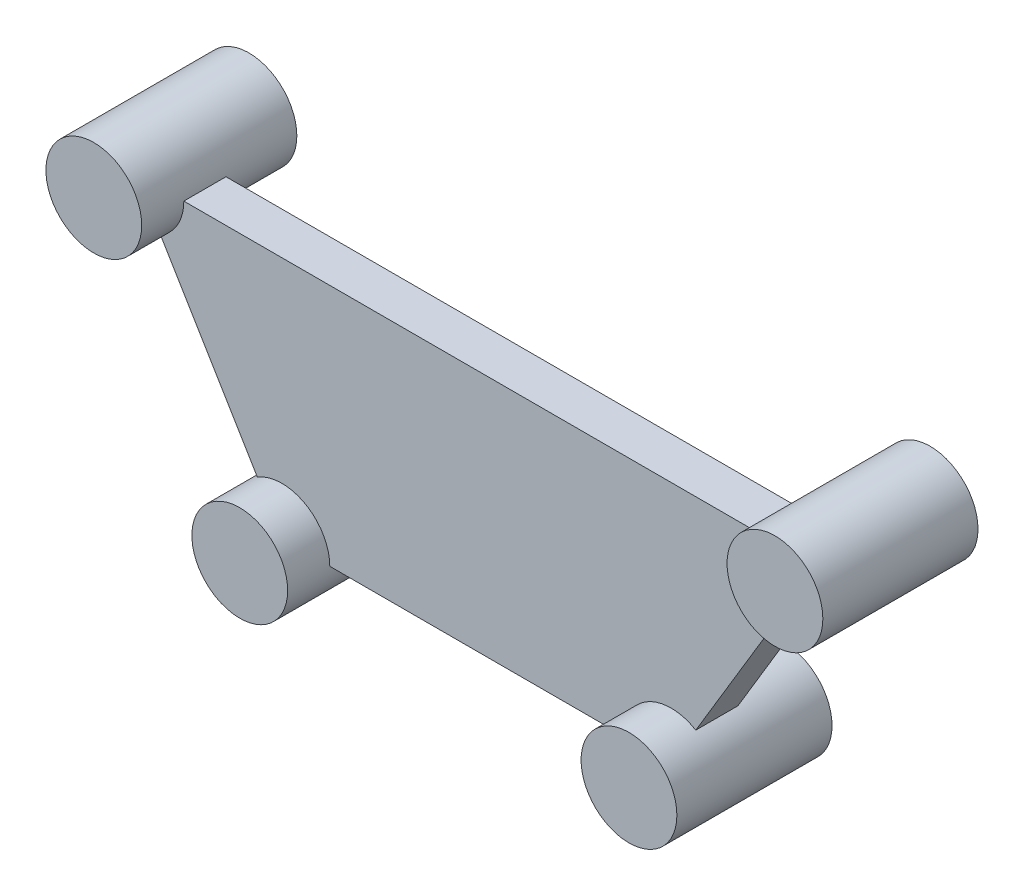
SolidWorks part; units mm, degrees
ref_plane "Front Plane" through (0, 0, 0) normal (0, 0, 1) x (1, 0, 0)
ref_plane "Top Plane" through (0, 0, 0) normal (0, 1, 0) x (1, 0, 0)
ref_plane "Right Plane" through (0, 0, 0) normal (1, 0, 0) x (0, 0, -1)
sketch "Sketch1" plane through (0, 0, 0) normal (0, 0, 1) x (1, 0, 0)
  line L0 (0, 281.6217) -> (0, -241.3025) construction
  line L1 (-177.8, 78.0624) -> (177.8, 78.0624)
  line L3 (101.6, -48.9376) -> (-101.6, -48.9376)
  line L4 (-101.6, -48.9376) -> (-177.8, 78.0624)
  line L5 (0, 78.0624) -> (0, -48.9376)
  line L6 (101.6, -48.9376) -> (177.8, 78.0624)
  circle A0 centre (177.8, 78.0624) radius 25
  circle A1 centre (101.6, -48.9376) radius 25
  circle A2 centre (-101.6, -48.9376) radius 25
  circle A3 centre (-177.8, 78.0624) radius 25
  dimension "D6" = 50
  dimension "D7" = 50
  dimension "D8" = 50
  dimension "D9" = 50
  dimension "D1" = 101.6
  dimension "D2" = 127
  dimension "D3" = 177.8
  dimension "D4" = 127
  dimension "D5" = 127
extrude "Boss-Extrude1" add sketch "Sketch1" along normal blind 22 contours L4 L1 L6 L3
extrude "Boss-Extrude2" add sketch "Sketch1<3>" along normal blind 44 and the other way blind 37 contours A0 | A1 | A2 | A3
sketch "Sketch1<3>" plane through (0, 0, 0) normal (0, 0, 1) x (1, 0, 0) same geometry as "Sketch1"
